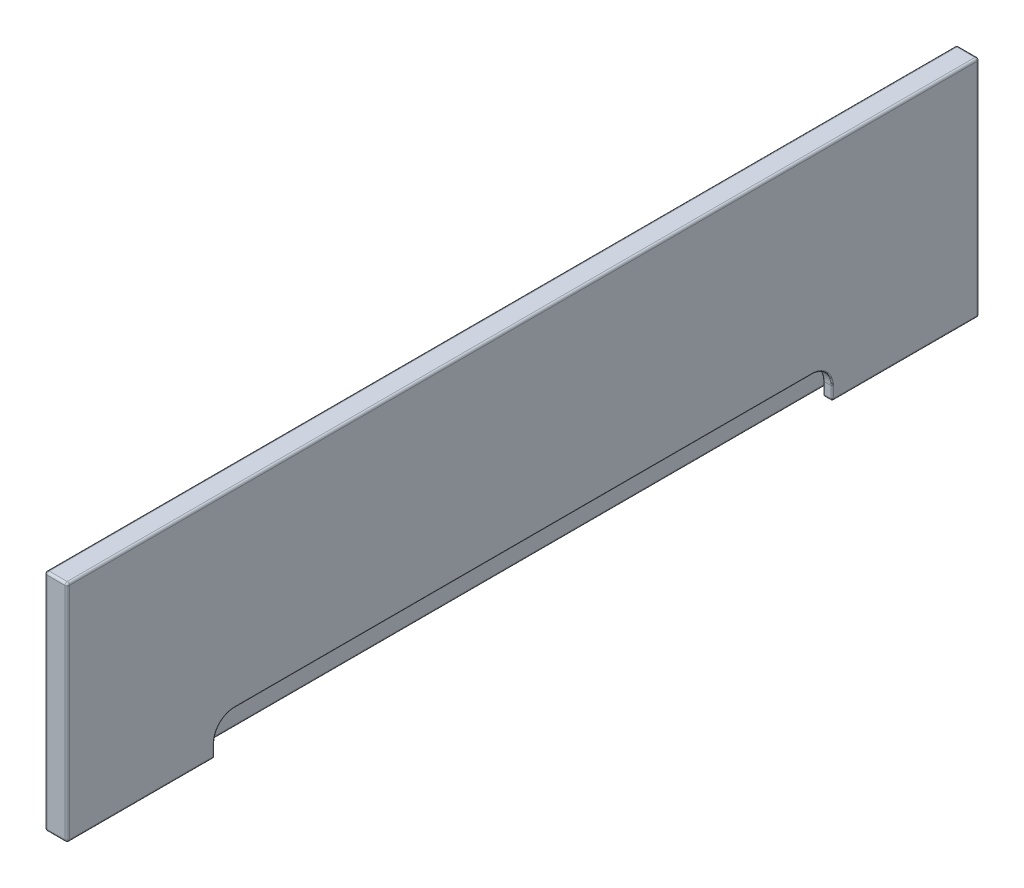
SolidWorks part; units mm, degrees
ref_plane "Front Plane" through (0, 0, 0) normal (0, 0, 1) x (1, 0, 0)
ref_plane "Top Plane" through (0, 0, 0) normal (0, 1, 0) x (1, 0, 0)
ref_plane "Right Plane" through (0, 0, 0) normal (1, 0, 0) x (0, 0, -1)
sketch "Sketch1" plane through (0, 0, 0) normal (1, 0, 0) x (0, 0, -1)
  line L1 (406, -100) -> (-406, -100)
  line L2 (406, -100) -> (406, 100)
  line L3 (406, 100) -> (-406, 100)
  line L4 (-406, -100) -> (-406, 100)
  line L5 (406, -100) -> (-406, 100) construction
  line L6 (406, 100) -> (-406, -100) construction
  point P0 (0, 0)
  dimension "D1" = 812
  dimension "D2" = 200
extrude "Boss-Extrude1" add sketch "Sketch1" against normal blind 20
sketch "Sketch3" plane through (0, 0, 0) normal (1, 0, 0) x (0, 0, -1)
  line L0 (-406, -100) -> (406, -100) construction
  line L1 (-275, -100) -> (275, -100)
  line L2 (-275, -100) -> (-275, -88)
  line L3 (-257, -70) -> (257, -70)
  line L4 (275, -100) -> (275, -88)
  arc A0 (257, -70) -> (275, -88) centre (257, -88) cw
  arc A1 (-275, -88) -> (-257, -70) centre (-257, -88) cw
  point P4 (0, -100)
  point P10 (275, -70)
  point P13 (-275, -70)
  dimension "D3" = 18
  dimension "D1" = 30
  dimension "D2" = 550
extrude "Cut-Extrude2" cut sketch "Sketch3" against normal blind 15
sketch "Sketch4" plane through (-15, 0, 0) normal (1, 0, 0) x (0, 0, -1)
  line L0 (-275, -100) -> (275, -100) construction
  line L1 (-285, -100) -> (285, -100)
  line L2 (-285, -100) -> (-285, -83)
  line L3 (-262, -60) -> (262, -60)
  line L4 (285, -100) -> (285, -83)
  arc A0 (262, -60) -> (285, -83) centre (262, -83) cw
  arc A1 (-285, -83) -> (-262, -60) centre (-262, -83) cw
  point P6 (0, -60)
  point P10 (285, -60)
  point P13 (-285, -60)
  dimension "D3" = 23
  dimension "D1" = 570
  dimension "D2" = 40
extrude "Cut-Extrude3" cut sketch "Sketch4" along normal blind 7
fillet "Fillet1" radius 1 20 edges at (-8, -91.5, -285) (-8, -66.7365, -278.2635) (-8, -60, 0) (-8, -91.5, 285) (0, -94, -275) (0, -75.2721, -269.7279) (0, -94, 275) (0, -75.2721, 269.7279) (-8, -94, -275) (-8, -75.2721, -269.7279) (-8, -94, 275) (-8, -75.2721, 269.7279) (-15, -91.5, -285) (-15, -66.7365, -278.2635) (-15, -91.5, 285) (-15, -66.7365, 278.2635) (-8, -66.7365, 278.2635) (0, -70, 0) (-8, -70, 0) (-15, -60, 0)
fillet "Fillet2" radius 2 28 edges at (-10, -100, -406) (-0.2929, -100, 275.2929) (-4, -100, 275) (-7.7071, -100, 275.2929) (-8, -100, 280) (-8.2929, -100, 284.7071) (-11.5, -100, 285) (-14.7071, -100, 284.7071) (-15, -100, 0) (-14.7071, -100, -284.7071) (-11.5, -100, -285) (-8.2929, -100, -284.7071) (-8, -100, -280) (-7.7071, -100, -275.2929) (-4, -100, -275) (-0.2929, -100, -275.2929) (-10, -100, 406) (-20, -100, 0) (-20, 0, -406) (-20, 0, 406) (-10, 100, 406) (-20, 100, 0) (-10, 100, -406) (0, -100, 341) (0, 0, 406) (0, 100, 0) (0, 0, -406) (0, -100, -341)
